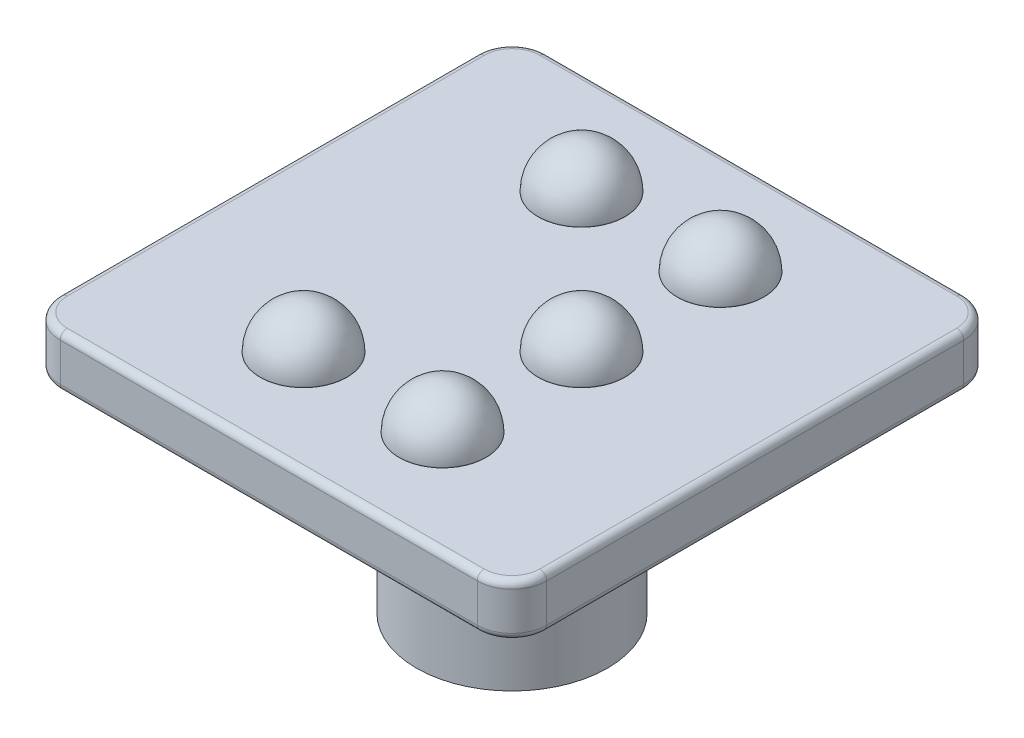
SolidWorks part; units mm, degrees
ref_plane "Front Plane" through (0, 0, 0) normal (0, 0, 1) x (1, 0, 0)
ref_plane "Top Plane" through (0, 0, 0) normal (0, 1, 0) x (1, 0, 0)
ref_plane "Right Plane" through (0, 0, 0) normal (1, 0, 0) x (0, 0, -1)
sketch "Sketch1" plane through (0, 0, 0) normal (0, 1, 0) x (1, 0, 0)
  line L1 (-7.3247, 4.3967) -> (4.6753, 4.3967)
  line L2 (-8.3247, 3.3967) -> (-8.3247, -8.6033)
  line L3 (-7.3247, -9.6033) -> (4.6753, -9.6033)
  line L4 (5.6753, 3.3967) -> (5.6753, -8.6033)
  arc A0 (-8.3247, -8.6033) -> (-7.3247, -9.6033) centre (-7.3247, -8.6033) ccw
  arc A1 (4.6753, -9.6033) -> (5.6753, -8.6033) centre (4.6753, -8.6033) ccw
  arc A2 (4.6753, 4.3967) -> (5.6753, 3.3967) centre (4.6753, 3.3967) cw
  arc A3 (-7.3247, 4.3967) -> (-8.3247, 3.3967) centre (-7.3247, 3.3967) ccw
  point P8 (5.6753, -9.6033)
  point P11 (5.6753, 4.3967)
  point P14 (-8.3247, 4.3967)
  dimension "D3" = 1
  dimension "D1" = 14
  dimension "D2" = 14
extrude "Boss-Extrude1" add sketch "Sketch1" along normal blind 1.5
sketch "Sketch2" plane through (0, 0, 0) normal (0, -1, 0) x (1, 0, 0)
  line L0 (-7.3247, 9.6033) -> (4.6753, 9.6033) construction
  line L1 (5.6753, 8.6033) -> (5.6753, -3.3967) construction
  line L2 (-1.3247, -4.3967) -> (-1.3247, 9.6033) construction
  line L3 (-8.3247, 2.6033) -> (5.6753, 2.6033) construction
  line L4 (-8.3247, -3.3967) -> (-8.3247, 8.6033) construction
  circle A0 centre (-1.3247, 2.6033) radius 2.75
  dimension "D1" = 7
  dimension "D2" = 7
extrude "Boss-Extrude2" add sketch "Sketch2" along normal blind 6
sketch "Sketch3" plane through (0, -6, 0) normal (0, -1, 0) x (1, 0, 0)
  line L0 (-1.3247, 5.3533) -> (-1.3247, -0.1467) construction
  line L1 (-3.3247, 3.1533) -> (0.6753, 3.1533)
  line L2 (-3.3247, 3.1533) -> (-3.3247, 2.0533)
  line L3 (-3.3247, 2.0533) -> (0.6753, 2.0533)
  line L4 (0.6753, 3.1533) -> (0.6753, 2.0533)
  line L5 (-1.8747, 4.6033) -> (-0.7747, 4.6033)
  line L6 (-1.8747, 4.6033) -> (-1.8747, 0.6033)
  line L7 (-1.8747, 0.6033) -> (-0.7747, 0.6033)
  line L8 (-0.7747, 4.6033) -> (-0.7747, 0.6033)
  line L9 (-4.0747, 2.6033) -> (1.4253, 2.6033) construction
  circle A3 centre (-1.3247, 2.6033) radius 2.75 construction
  circle A4 centre (-1.3247, 2.6033) radius 2.75 construction
  dimension "D7" = 0.55
  dimension "D1" = 4
  dimension "D2" = 1.1
  dimension "D3" = 1.1
  dimension "D4" = 4
  dimension "D8" = 0.55
extrude "Cut-Extrude1" cut sketch "Sketch3" against normal blind 6 contours L8 L5 L6 L1 | L1 L8 L3 L4 | L8 L1 L6 L3 | L6 L1 L2 L3 | L8 L3 L6 L7 region at (-2.5997, -6, 2.6033) region at (-1.3247, -6, 3.8783) region at (-1.3247, -6, 2.6033) region at (-0.0497, -6, 2.6033) region at (-1.3247, -6, 1.3283)
chamfer "Chamfer1" distance 0.3 angle 45 12 edges at (-1.3247, -6, 0.6033) (-1.8747, -6, 1.3283) (-2.5997, -6, 2.0533) (-3.3247, -6, 2.6033) (-2.5997, -6, 3.1533) (-0.7747, -6, 1.3283) (-0.0497, -6, 2.0533) (0.6753, -6, 2.6033) (-0.0497, -6, 3.1533) (-0.7747, -6, 3.8783) (-1.3247, -6, 4.6033) (-1.8747, -6, 3.8783)
fillet "Fillet1" radius 1 1 edges at (-1.3247, 0, -0.1467)
sketch "Sketch4" plane through (0, 1.5, 0) normal (0, 1, 0) x (1, 0, 0)
  line L0 (-1.3247, 4.3967) -> (-1.3247, -9.6033) construction
  line L1 (4.6753, 4.3967) -> (-7.3247, 4.3967) construction
  line L2 (-7.3247, -9.6033) -> (4.6753, -9.6033) construction
  line L3 (5.6753, -2.6033) -> (-8.3247, -2.6033) construction
  line L4 (-8.3247, 3.3967) -> (-8.3247, -8.6033) construction
  line L5 (5.6753, -8.6033) -> (5.6753, 3.3967) construction
  line L6 (-3.3247, 4.3967) -> (-3.3247, -9.6033) construction
  line L7 (0.6753, 4.3967) -> (0.6753, -9.6033) construction
  line L8 (-8.3247, 1.3967) -> (5.6753, 1.3967) construction
  line L9 (5.6753, -6.6033) -> (-8.3247, -6.6033) construction
  circle A0 centre (-3.3247, 1.3967) radius 1.25
  circle A1 centre (0.6753, -2.6033) radius 1.25
  circle A3 centre (-3.3247, -6.6033) radius 1.25
  circle A4 centre (0.6753, -6.6033) radius 1.25
  circle A5 centre (0.6753, 1.3967) radius 1.25
  dimension "D1" = 4
  dimension "D2" = 4
  dimension "D3" = 2
  dimension "D4" = 2
extrude "Boss-Extrude3" add sketch "Sketch4" along normal blind 0.01
dome "Dome1" faces to dome 1 distance 1.25 reverse direction no elliptical dome no face at (-3.3247, 1.51, -0.1467) parameters "D1"=1.25
dome "Dome2" faces to dome 1 distance 1.25 reverse direction no elliptical dome no face at (0.6753, 1.51, -0.1467) parameters "D1"=1.25
dome "Dome4" faces to dome 1 distance 1.25 reverse direction no elliptical dome no face at (0.6753, 1.51, 3.8533) parameters "D1"=1.25
dome "Dome5" faces to dome 1 distance 1.25 reverse direction no elliptical dome no face at (-3.3247, 1.51, 7.8533) parameters "D1"=1.25
dome "Dome6" faces to dome 1 distance 1.25 reverse direction no elliptical dome no face at (0.6753, 1.51, 7.8533) parameters "D1"=1.25
fillet "Fillet3" radius 0.2 16 edges at (5.3824, 1.5, -4.1038) (5.6753, 1.5, 2.6033) (5.3824, 1.5, 9.3104) (-1.3247, 1.5, 9.6033) (-8.0318, 1.5, 9.3104) (-8.0318, 1.5, -4.1038) (-8.3247, 1.5, 2.6033) (-1.3247, 1.5, -4.3967) (5.3824, 0, 9.3104) (5.6753, 0, 2.6033) (5.3824, 0, -4.1038) (-1.3247, 0, -4.3967) (-8.0318, 0, -4.1038) (-8.3247, 0, 2.6033) (-8.0318, 0, 9.3104) (-1.3247, 0, 9.6033)
